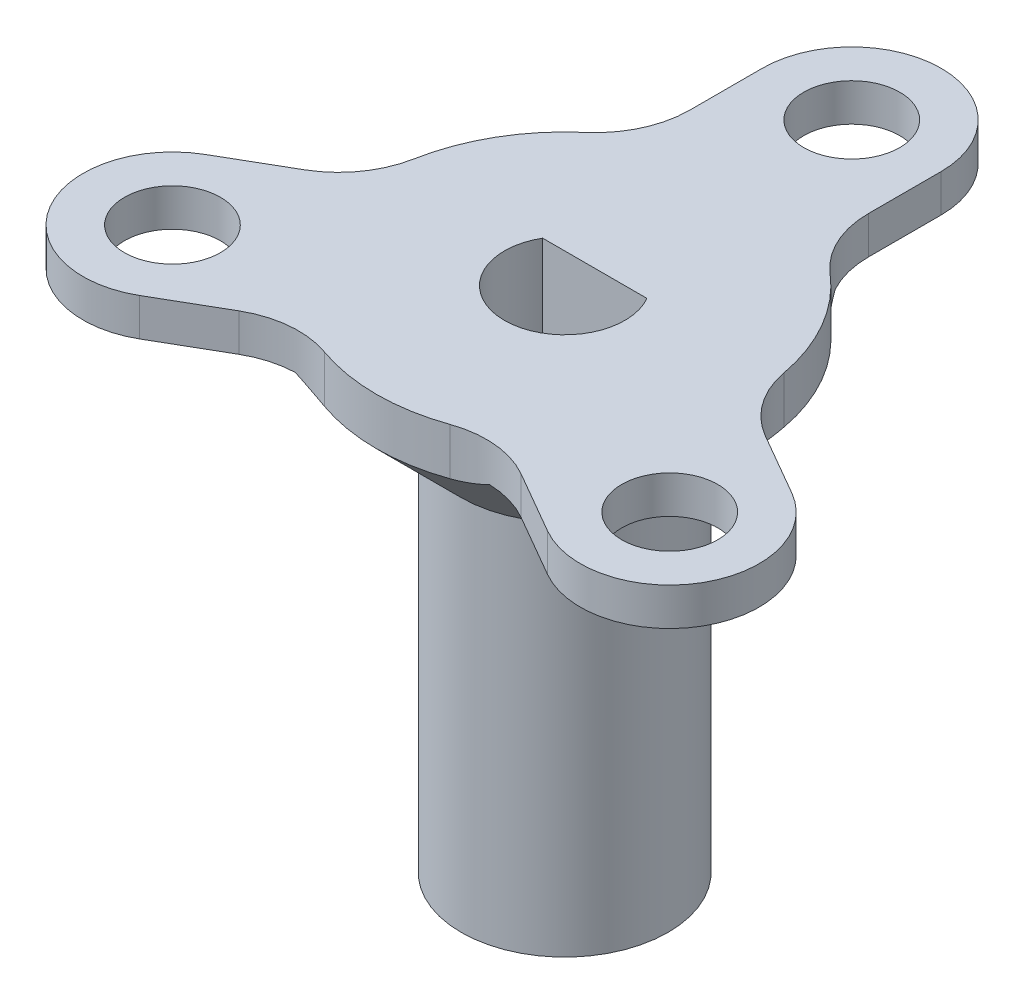
SolidWorks part; units mm, degrees
ref_plane "Front Plane" through (0, 0, 0) normal (0, 0, 1) x (1, 0, 0)
ref_plane "Top Plane" through (0, 0, 0) normal (0, 1, 0) x (1, 0, 0)
ref_plane "Right Plane" through (0, 0, 0) normal (1, 0, 0) x (0, 0, -1)
sketch "Sketch1" plane through (0, 0, 0) normal (0, 1, 0) x (1, 0, 0)
  circle A0 centre (0, 0) radius 10
  dimension "D1" = 20
extrude "Boss-Extrude1" add sketch "Sketch1" along normal blind 2
sketch "Sketch2" plane through (0, 2, 0) normal (0, 1, 0) x (1, 0, 0)
  line L0 (-4.75, 15.25) -> (-4.75, 8.7999)
  line L1 (4.75, 15.25) -> (4.75, 8.7999)
  circle A0 centre (0, 15.25) radius 2.55
  arc A1 (4.75, 15.25) -> (-4.75, 15.25) centre (0, 15.25) ccw
  circle A2 centre (0, 0) radius 10 construction
  arc A3 (-4.75, 8.7999) -> (4.75, 8.7999) centre (0, 0) cw
  dimension "D1" = 5.1
  dimension "D2" = 9.5
  dimension "D3" = 15.25
extrude "Boss-Extrude2" add sketch "Sketch2" against normal up to surface (2 mm away) up to face at (0, 0, 10)
pattern_circular "CirPattern1" count 3 over 360 about axis through (0, 2, 0) along (0, -1, 0) of "Boss-Extrude2"
sketch "Sketch3" plane through (0, 2, 0) normal (0, 1, 0) x (1, 0, 0)
  line L0 (-2.6533, 1.4) -> (2.6533, 1.4)
  arc A0 (-2.6533, 1.4) -> (2.6533, 1.4) centre (0, 0) ccw
  dimension "D1" = 6
  dimension "D2" = 1.4
extrude "Cut-Extrude1" cut sketch "Sketch3" against normal through all
sketch "Sketch4" plane through (0, 0, 0) normal (0, -1, 0) x (1, 0, 0)
  line L0 (2.6533, -1.4) -> (-2.6533, -1.4) construction
  line L1 (2.6533, -1.4) -> (-2.6533, -1.4)
  circle A1 centre (0, 0) radius 5.5
  arc A3 (2.6533, -1.4) -> (-2.6533, -1.4) centre (0, 0) ccw construction
  arc A4 (2.6533, -1.4) -> (-2.6533, -1.4) centre (0, 0) ccw
  dimension "D1" = 2.5
extrude "Boss-Extrude3" add sketch "Sketch4" along normal blind 25
sketch "Sketch5" plane through (0, -25, 0) normal (0, -1, 0) x (1, 0, 0)
  circle A0 centre (0, 0) radius 3
  arc A1 (2.6533, -1.4) -> (-2.6533, -1.4) centre (0, 0) ccw construction
extrude "Cut-Extrude2" cut sketch "Sketch5" against normal blind 7
sketch "Sketch7" plane through (0, -18, 0) normal (0, -1, 0) x (1, 0, 0)
  line L0 (2.6533, -1.4) -> (-2.6533, -1.4) construction
  line L1 (2.6533, -1.4) -> (-2.6533, -1.4)
  line L2 (2.7713, -1.6) -> (-2.7713, -1.6)
  circle A0 centre (0, 0) radius 3 construction
  arc A1 (2.6533, -1.4) -> (-2.6533, -1.4) centre (0, 0) ccw
  arc A2 (2.7713, -1.6) -> (-2.7713, -1.6) centre (0, 0) ccw
  dimension "D1" = 0.2
extrude "Cut-Extrude3" cut sketch "Sketch7" against normal through all and the other way through all
sketch "Sketch8" plane through (0, -25, 0) normal (0, -1, 0) x (1, 0, 0)
  circle A0 centre (0, 0) radius 3.2
  arc A1 (2.7713, -1.6) -> (-2.7713, -1.6) centre (0, 0) ccw construction
extrude "Cut-Extrude4" cut sketch "Sketch8" against normal up to surface (7 mm away) up to face at (0, -18, -2.3)
fillet "Fillet2" radius 5 6 edges at (-4.75, 1, -8.7999) (-9.9959, 1, 0.2863) (-5.2459, 1, 8.5135) (5.2459, 1, 8.5135) (9.9959, 1, 0.2863) (4.75, 1, -8.7999)
chamfer "Chamfer1" distance 5 angle 45 1 edges at (0, 0, 5.5)
